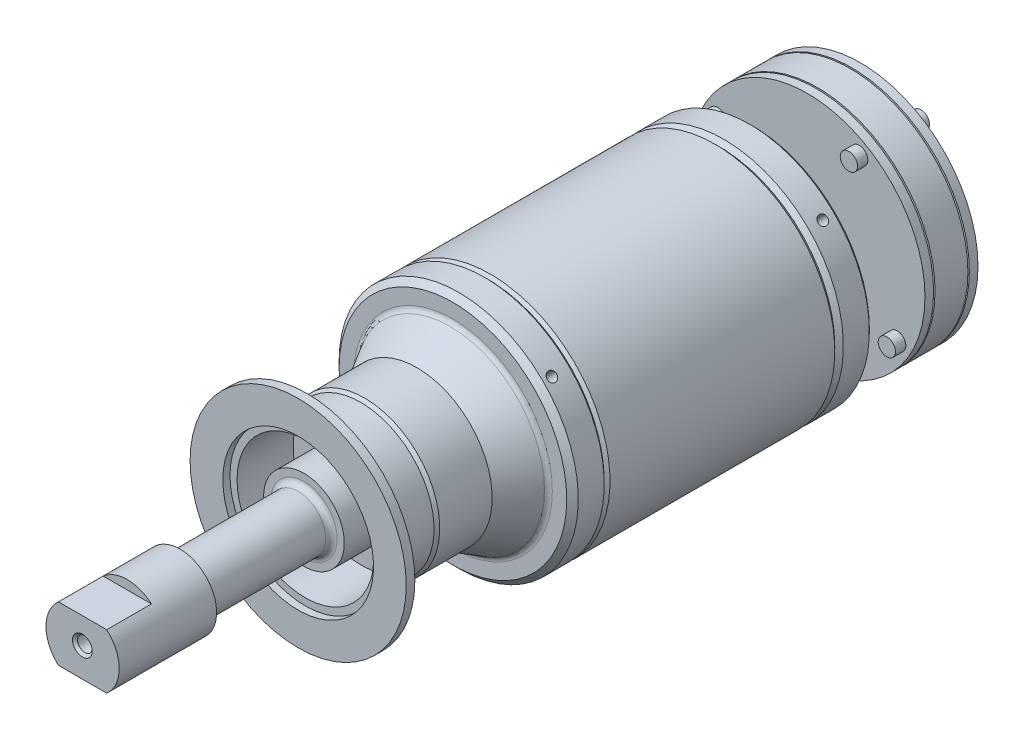
SolidWorks part; units mm, degrees
ref_plane "front" through (0, 0, 0) normal (0, 0, 1) x (1, 0, 0)
ref_plane "top" through (0, 0, 0) normal (0, 1, 0) x (1, 0, 0)
ref_plane "right" through (0, 0, 0) normal (1, 0, 0) x (0, 0, -1)
ref_axis "Axis1" through (0, 0, -80.9) along (0, 0, 1)
ref_plane "Plane1" through (0, 0, 0) normal (-0.7071, 0.7071, 0) x (-0.7071, -0.7071, 0)
sketch "Sketch1" plane through (0, 0, 0) normal (1, 0, 0) x (0, 0, -1)
  line L0 (-96.8, 0) -> (178.8, 0)
  line L1 (173.1, 6.3) -> (173.1, 40.8)
  line L2 (169.6, 40.8) -> (158.2, 40.8)
  line L3 (154.7, 40.8) -> (154.7, 6.3)
  line L4 (154.7, 6.3) -> (137.7, 6.3)
  line L5 (135.7, 41.5) -> (125.7, 41.5)
  line L6 (137.7, 6.3) -> (137.7, 7)
  line L7 (137.7, 7) -> (135.7, 7)
  line L8 (135.7, 7) -> (135.7, 41.5)
  line L9 (157.7, 40.8) -> (157.7, 37.8)
  line L10 (0, 23.7109) -> (-19.5, 23.7109)
  line L11 (173.1, 6.3) -> (174.1, 6.3)
  line L12 (-22, 26.15) -> (-22, 37.5)
  line L13 (-22, 37.5) -> (-19, 37.5)
  line L14 (-19, 37.5) -> (-15.7578, 25.4)
  line L15 (0, 23.7109) -> (0, 14)
  line L16 (174.1, 6.3) -> (174.1, 4.25)
  line L17 (174.1, 4.25) -> (178.8, 4.25)
  line L18 (-63, 12.7) -> (-96.8, 12.7)
  line L19 (-96.8, 12.7) -> (-96.8, 0)
  line L20 (-96.8, 0) -> (-142.9002, 0) construction
  line L21 (-63, 12.7) -> (-63, 9.525)
  line L22 (-63, 9.525) -> (-20, 9.525)
  line L23 (-20, 9.525) -> (-20, 14)
  line L24 (-20, 14) -> (0, 14)
  line L25 (178.8, 4.25) -> (178.8, 0)
  line L26 (-15.7578, 25.4) -> (-0.2538, 25.4)
  line L27 (125.7, 41.5) -> (124.2, 40)
  line L28 (124.2, 40) -> (122.7, 41.5)
  line L29 (44.7, 41.5) -> (43.7, 40.5)
  line L30 (43.7, 40.5) -> (42.7, 41.5)
  line L31 (122.7, 41.5) -> (44.7, 41.5)
  line L32 (42.7, 41.5) -> (33.7, 41.5)
  line L33 (31.7, 39.5) -> (33.7, 41.5)
  line L34 (157.7, 37.8) -> (158.2, 37.8)
  line L35 (31.7, 39.5) -> (31.7, 34.4955)
  line L36 (30.7, 32.7634) -> (19.2, 26.1239)
  line L37 (19.2, 26.1239) -> (1, 26.1239)
  line L38 (1, 26.1239) -> (-0.2538, 25.4)
  line L39 (158.2, 37.8) -> (158.2, 40.8)
  line L40 (-22, 26.15) -> (-19.5, 26.15)
  line L41 (-19.5, 26.15) -> (-19.5, 23.7109)
  line L42 (34.2, 40) -> (34.2, 0) construction
  line L43 (157.7, 40.8) -> (154.7, 40.8)
  line L44 (169.6, 40.8) -> (169.6, 37.8)
  line L45 (169.6, 37.8) -> (170.1, 37.8)
  line L46 (170.1, 37.8) -> (170.1, 40.8)
  line L47 (170.1, 40.8) -> (173.1, 40.8)
  arc A0 (31.7, 34.4955) -> (30.7, 32.7634) centre (29.7, 34.4955) cw
  dimension "D24" = 2
  dimension "D1" = 83
  dimension "D3" = 75
  dimension "D4" = 30
  dimension "D5" = 2
  dimension "D6" = 8.5
  dimension "D7" = 12.6
  dimension "D8" = 28
  dimension "D9" = 10
  dimension "D10" = 25.4
  dimension "D11" = 81.6
  dimension "D12" = 4.7
  dimension "D13" = 20
  dimension "D14" = 11
  dimension "D15" = 96.8
  dimension "D16" = 19.05
  dimension "D17" = 33.8
  dimension "D18" = 1
  dimension "D19" = 43.1
  dimension "D20" = 18.4
  dimension "D21" = 232.5
  dimension "D22" = 3
  dimension "D23" = 18.2
  dimension "D25" = 2
  dimension "D26" = 45
  dimension "D27" = 104
  dimension "D28" = 19.2
  dimension "D29" = 31.7
  dimension "D30" = 1
  dimension "D31" = 19
  dimension "D32" = 15
  dimension "D33" = 3
  dimension "D34" = 50.8
  dimension "D35" = 2.413
  dimension "D36" = 74.8
  dimension "D37" = 2
  dimension "D38" = 14
  dimension "D39" = 52.3
  dimension "D40" = 2.5
  dimension "D41" = 52.2478
  dimension "D42" = 23
  dimension "D43" = 53.7
  dimension "D44" = 0.5
  dimension "D45" = 3
revolve "Revolve1" add sketch "Sketch1" angle 360 about L20
sketch "Sketch2" plane through (0, 0, 0) normal (1, 0, 0) x (0, 0, -1)
  line L0 (-81.3, 20) -> (-81.3, 9.55)
  line L1 (-81.3, 9.55) -> (-111.3, 9.55)
  line L2 (-111.3, 9.55) -> (-111.3, -9.55)
  line L3 (-121.3, -20) -> (-121.3, 20)
  line L4 (-121.3, 20) -> (-81.3, 20)
  line L5 (-121.3, 0) -> (-153.2842, 0) construction
  line L6 (-81.3, -9.55) -> (-111.3, -9.55)
  line L7 (-81.3, -20) -> (-81.3, -9.55)
  line L8 (-121.3, -20) -> (-81.3, -20)
  line L9 (-96.8, 12.7) -> (-96.8, 0) construction
  dimension "D1" = 19.1
  dimension "D2" = 15.5
  dimension "D3" = 40
  dimension "D4" = 10
  dimension "D5" = 40
extrude "Extrude1" cut sketch "Sketch2" against normal mid plane 40
fillet "Fillet1" radius 2 2 edges at (-9.525, 0, 20) (-9.525, 0, 63)
chamfer "Chamfer2" distance 1 angle 45 1 edges at (-41.5, 0, -135.7)
hole_wizard "1/4-20 Tapped Hole1" positions "Sketch4" profile "Sketch3" tap size "1/4-20" standard "Ansi Inch"
sketch "Sketch4" plane through (0, 0, 96.8) normal (0, 0, 1) x (1, 0, 0)
  point P0 (-0.0774, 0.5605)
sketch "Sketch3" plane through (-0.0774, 0.5605, 96.8) normal (1, 0, 0) x (0, -1, 0)
  line L0 (0, 0) -> (0, 20.5838)
  line L1 (0, 20.5838) -> (2.5527, 19.05)
  line L2 (2.5527, 19.05) -> (2.5527, 0.8763)
  line L3 (2.5527, 0.8763) -> (3.429, 0)
  line L5 (3.429, 0) -> (0, 0)
  line L6 (-2.5527, 0.8763) -> (-3.429, 0) construction
  line L10 (0, 20.5838) -> (-2.5527, 19.05) construction
  line L11 (0, -6.35) -> (0, 107.95) construction
  dimension "Tap Drill Dia." = 5.1054
  dimension "Tap Drill Depth" = 19.05
  dimension "Near C'Sink Dia." = 6.858
  dimension "Near C'Sink Angle" = 90
  dimension "Drill Angle" = 118
cosmetic thread "Hole Thread1" parameters "D1"=12.7, "D2"=6.35
sketch "Sketch6" plane through (0, 0, 0) normal (1, 0, 0) x (0, 0, -1)
  line L0 (0, 0) -> (-119.8951, 0) construction
  line L2 (3.2, 35) -> (18.2, 35)
  line L3 (3.2, 35) -> (3.2, 25)
  line L4 (3.2, 25) -> (18.2, 25)
  line L5 (18.2, 35) -> (18.2, 25)
  line L6 (10.7, 35) -> (10.7, 25) construction
  line L7 (-96.8, 9.55) -> (-96.8, -9.55) construction
  dimension "D1" = 107.5
  dimension "D2" = 15
  dimension "D3" = 70
  dimension "D4" = 50
revolve "Revolve2" [suppressed] add sketch "Sketch6" angle 360 about L0
sketch "Sketch8" plane through (0, 0, 0) normal (1, 0, 0) x (0, 0, -1)
  circle A0 centre (10.5, 0) radius 4.7625
  circle A1 centre (10.5, 0) radius 3.175
  dimension "D1" = 9.525
  dimension "D2" = 6.35
  dimension "D3" = 10.5
extrude "Boss-Extrude2" [suppressed] add sketch "Sketch8" along normal blind 66 and the other way blind 66
hole_wizard "M4x0.7 Tapped Hole1" positions "3DSketch1" profile "Sketch9" tap size "M4x0.7" standard "Ansi Metric"
sketch3d "3DSketch1"
  point P0 (29.3449, 29.3449, -130.7)
  dimension "D1" = 5
sketch "Sketch9" plane through (29.3449, 29.3449, -130.7) normal (0, 0, 1) x (-0.7071, 0.7071, 0)
  line L0 (0, 0) -> (0, 10.9914)
  line L1 (0, 10.9914) -> (1.65, 10)
  line L2 (1.65, 10) -> (1.65, 0)
  line L5 (1.65, 0) -> (0, 0)
  line L10 (0, 10.9914) -> (-1.65, 10) construction
  line L11 (0, -6.35) -> (0, 107.95) construction
  dimension "Tap Drill Dia." = 3.3
  dimension "Tap Drill Depth" = 10
  dimension "Drill Angle" = 118
cosmetic thread "Hole Thread2" parameters "D1"=8, "D2"=4
hole_wizard "M4x0.7 Tapped Hole2" positions "3DSketch2" profile "Sketch10" tap size "M4x0.7" standard "Ansi Metric"
sketch3d "3DSketch2"
  point P0 (29.3449, 29.3449, -36.7)
  dimension "D1" = 99
sketch "Sketch10" plane through (29.3449, 29.3449, -36.7) normal (0, 0, 1) x (-0.7071, 0.7071, 0)
  line L0 (0, 0) -> (0, 11.0914)
  line L1 (0, 11.0914) -> (1.65, 10.1)
  line L2 (1.65, 10.1) -> (1.65, 0)
  line L5 (1.65, 0) -> (0, 0)
  line L10 (0, 11.0914) -> (-1.65, 10.1) construction
  line L11 (0, -6.35) -> (0, 107.95) construction
  dimension "Tap Drill Dia." = 3.3
  dimension "Tap Drill Depth" = 10.1
  dimension "Drill Angle" = 118
cosmetic thread "Hole Thread3" parameters "D1"=8, "D2"=4
pattern_circular "CirPattern2" count 4 over 360 about axis through (0, 0, -80.9) along (0, 0, 1) of "M4x0.7 Tapped Hole1", "M4x0.7 Tapped Hole2"
sketch "Sketch11" plane through (0, 0, -173.1) normal (0, 0, -1) x (-1, 0, 0)
  line L0 (0, 23.304) -> (0, 11.5752) construction
  line L1 (-12.8589, 22.2722) -> (-5.6298, 9.7511) construction
  circle A0 centre (-17.9959, 31.1698) radius 3
  dimension "D1" = 6
  dimension "D3" = 35.9918
  dimension "D2" = 30
extrude "Boss-Extrude3" add sketch "Sketch11" along normal blind 3 and the other way blind 22
pattern_circular "CirPattern3" count 4 over 360 about axis through (0, 0, -80.9) along (0, 0, 1) of "Boss-Extrude3"
